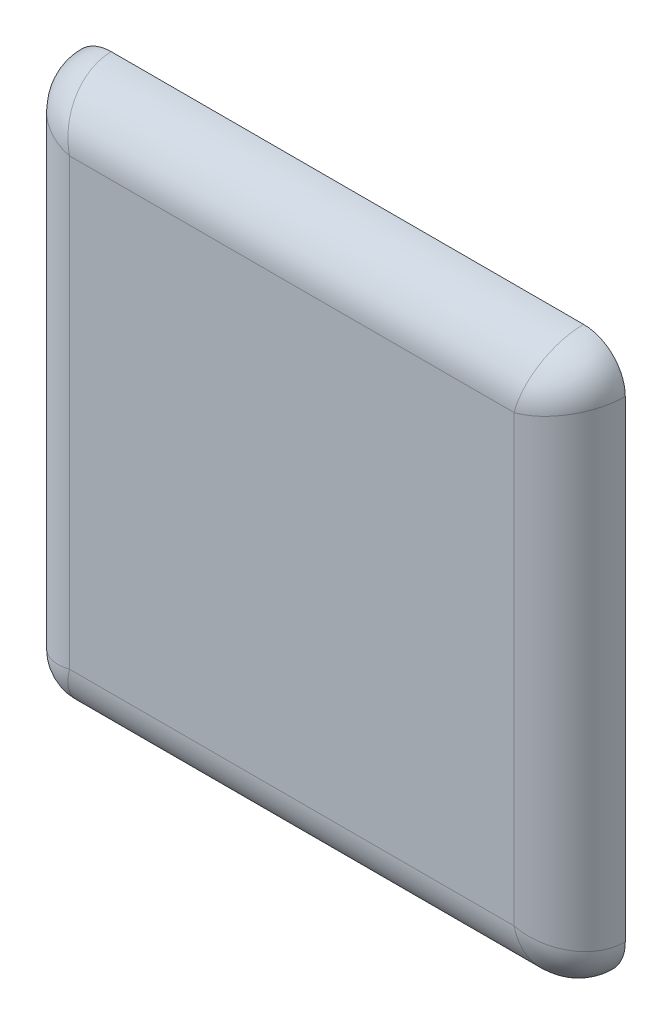
SolidWorks part; units mm, degrees
material "PE High Density"
ref_plane "Front Plane" through (0, 0, 0) normal (0, 0, 1) x (1, 0, 0)
ref_plane "Top Plane" through (0, 0, 0) normal (0, 1, 0) x (1, 0, 0)
ref_plane "Right Plane" through (0, 0, 0) normal (1, 0, 0) x (0, 0, -1)
sketch "Sketch1" plane through (0, 0, 0) normal (0, 0, 1) x (1, 0, 0)
  line L1 (1.5, 0) -> (18.5, 0)
  line L2 (0, 1.5) -> (0, 18.5)
  line L3 (1.5, 20) -> (18.5, 20)
  line L4 (20, 1.5) -> (20, 18.5)
  arc A0 (0, 18.5) -> (1.5, 20) centre (1.5, 18.5) cw
  arc A1 (18.5, 20) -> (20, 18.5) centre (18.5, 18.5) cw
  arc A2 (18.5, 0) -> (20, 1.5) centre (18.5, 1.5) ccw
  arc A3 (1.5, 0) -> (0, 1.5) centre (1.5, 1.5) cw
  point P11 (20, 0)
  point P14 (0, 0)
  dimension "D2" = 1.5
  dimension "D1" = 20
extrude "Main Body" add sketch "Sketch1" along normal blind 2
fillet "Fillet1" radius 2 8 edges at (0.4393, 0.4393, 2) (0, 10, 2) (0.4393, 19.5607, 2) (10, 20, 2) (19.5607, 19.5607, 2) (20, 10, 2) (19.5607, 0.4393, 2) (10, 0, 2)
